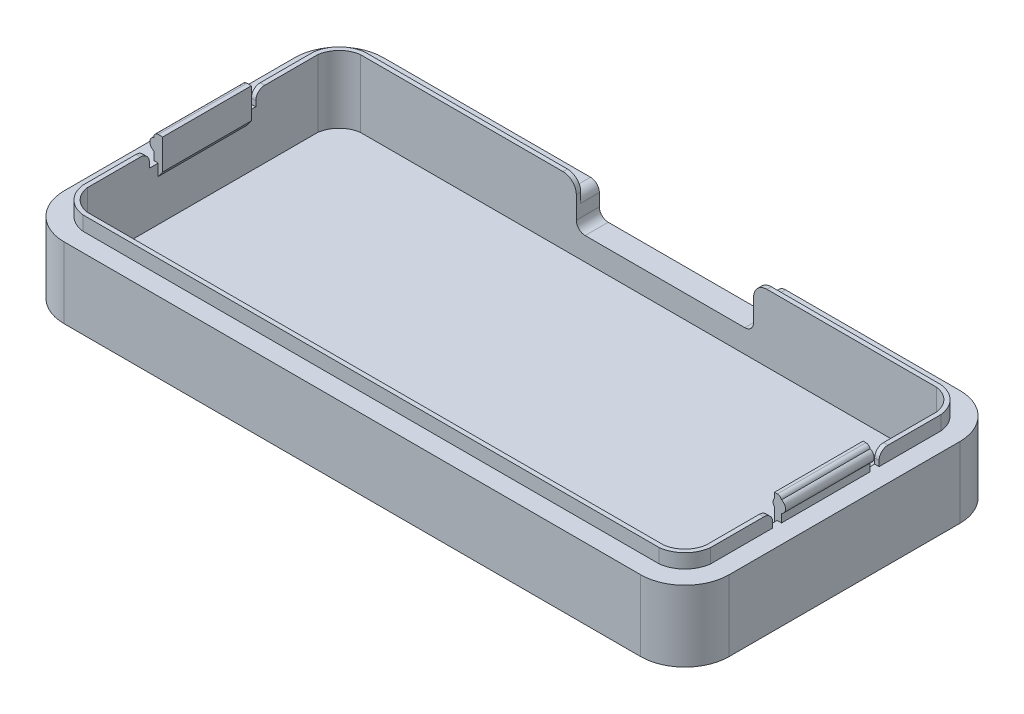
SolidWorks part; units mm, degrees
ref_plane "前视基准面" through (0, 0, 0) normal (0, 0, 1) x (1, 0, 0)
ref_plane "上视基准面" through (0, 0, 0) normal (0, 1, 0) x (1, 0, 0)
ref_plane "右视基准面" through (0, 0, 0) normal (1, 0, 0) x (0, 0, -1)
sketch "zero" plane through (0, 0, 0) normal (0, 1, 0) x (1, 0, 0)
  line L1 (-29.5, 15) -> (29.5, 15)
  line L2 (-32.5, 12) -> (-32.5, -12)
  line L3 (-29.5, -15) -> (29.5, -15)
  line L4 (32.5, 12) -> (32.5, -12)
  line L5 (-32.5, 15) -> (32.5, -15) construction
  line L6 (-32.5, -15) -> (32.5, 15) construction
  line L7 (-25.7, -15) -> (-14.5, -15)
  line L8 (-25.7, -15) -> (-25.7, -9.6569)
  line L9 (-25.7, -9.6569) -> (-14.5, -9.6569)
  line L10 (-14.5, -15) -> (-14.5, -9.6569)
  line L11 (5.2, -15) -> (12.7, -15)
  line L12 (5.2, -15) -> (5.2, -11)
  line L13 (5.2, -11) -> (12.7, -11)
  line L14 (12.7, -15) -> (12.7, -11)
  line L15 (17.8, -15) -> (25.3, -15)
  line L16 (17.8, -15) -> (17.8, -11)
  line L17 (17.8, -11) -> (25.3, -11)
  line L18 (25.3, -15) -> (25.3, -11)
  line L19 (-32.5, 7.7) -> (-19.5, 7.7)
  line L20 (-32.5, 7.7) -> (-32.5, -4.3)
  line L21 (-32.5, -4.3) -> (-19.5, -4.3)
  line L22 (-19.5, 7.7) -> (-19.5, -4.3)
  line L23 (-25.5, 14) -> (25.5, 14)
  line L24 (-25.5, 14) -> (-25.5, 8.8)
  line L25 (-25.5, 8.8) -> (25.5, 8.8)
  line L26 (25.5, 14) -> (25.5, 8.8)
  line L27 (-19.5, 7.2329) -> (-35.5, 7.2329)
  line L28 (-19.5, 7.2329) -> (-19.5, -3.7671)
  line L29 (-19.5, -3.7671) -> (-35.5, -3.7671)
  line L30 (-35.5, 7.2329) -> (-35.5, -3.7671)
  arc A0 (29.5, -15) -> (32.5, -12) centre (29.5, -12) ccw
  arc A1 (29.5, 15) -> (32.5, 12) centre (29.5, 12) cw
  arc A2 (-32.5, -12) -> (-29.5, -15) centre (-29.5, -12) ccw
  arc A3 (-29.5, 15) -> (-32.5, 12) centre (-29.5, 12) ccw
  circle A4 centre (-29, 11.4) radius 3
  circle A5 centre (-29, -11.5) radius 3
  circle A6 centre (29, 11.4) radius 3
  circle A7 centre (29, -11.5) radius 3
  circle A8 centre (-29, 11.4) radius 1.375
  circle A9 centre (-29, -11.5) radius 1.375
  circle A10 centre (29, -11.5) radius 1.375
  circle A11 centre (29, 11.4) radius 1.375
  point P0 (0, 0)
  dimension "D3" = 3
  dimension "D4" = 6
  dimension "D9" = 2.75
  dimension "D1" = 65
  dimension "D2" = 30
  dimension "D5" = 3.6
  dimension "D6" = 3.5
  dimension "D7" = 3.5
  dimension "D8" = 3.5
  dimension "D10" = 12
  dimension "D11" = 7.3
  dimension "D12" = 13
  dimension "D13" = 11.2
  dimension "D14" = 6.8
  dimension "D15" = 19.7
  dimension "D16" = 7.5
  dimension "D17" = 7.5
  dimension "D18" = 5.1
  dimension "D19" = 4
  dimension "D20" = 5.2
  dimension "D21" = 7
  dimension "D22" = 7
  dimension "D23" = 1
  dimension "D24" = 11
  dimension "D25" = 16
sketch "sugar" plane through (0, 0, 0) normal (0, 1, 0) x (1, 0, 0)
  line L1 (-29.5, 15) -> (29.5, 15)
  line L2 (-32.5, 12) -> (-32.5, -12)
  line L3 (-29.5, -15) -> (29.5, -15)
  line L4 (32.5, 12) -> (32.5, -12)
  line L5 (-32.5, 15) -> (32.5, -15) construction
  line L6 (-32.5, -15) -> (32.5, 15) construction
  line L7 (23.5, -11.5) -> (19.5, -11.5)
  line L8 (23.5, -11.5) -> (23.5, -13.9082)
  line L9 (23.5, -13.9082) -> (19.5, -13.9082)
  line L10 (19.5, -11.5) -> (19.5, -13.9082)
  line L11 (16, -11.0071) -> (8.5, -11.0071)
  line L12 (16, -11.0071) -> (16, -15)
  line L13 (16, -15) -> (8.5, -15)
  line L14 (8.5, -11.0071) -> (8.5, -15)
  line L15 (20.5, -13.9082) -> (22.5, -13.9082)
  line L16 (20.5, -13.9082) -> (20.5, -14.8173)
  line L17 (20.5, -14.8173) -> (22.5, -14.8173)
  line L18 (22.5, -13.9082) -> (22.5, -14.8173)
  arc A0 (29.5, 15) -> (32.5, 12) centre (29.5, 12) cw
  arc A1 (29.5, -15) -> (32.5, -12) centre (29.5, -12) ccw
  arc A2 (-32.5, -12) -> (-29.5, -15) centre (-29.5, -12) ccw
  arc A3 (-29.5, 15) -> (-32.5, 12) centre (-29.5, 12) ccw
  circle A4 centre (-29, 11.4) radius 3
  circle A5 centre (-29, 11.4) radius 1.375
  circle A6 centre (-29, -11.5) radius 3
  circle A7 centre (-29, -11.5) radius 1.375
  circle A8 centre (29, 11.4) radius 3
  circle A9 centre (29, 11.4) radius 1.375
  circle A10 centre (29, -11.5) radius 3
  circle A11 centre (29, -11.5) radius 1.375
  dimension "D3" = 3
  dimension "D1" = 65
  dimension "D2" = 30
  dimension "D4" = 9
  dimension "D5" = 4
  dimension "D6" = 3.5
  dimension "D7" = 7.5
  dimension "D8" = 2
  dimension "D9" = 1
sketch "case" plane through (0, 0, 0) normal (0, 1, 0) x (1, 0, 0)
  line L1 (-34.0422, 18) -> (30.9578, 18)
  line L2 (-39.0422, 13) -> (-39.0422, -13)
  line L3 (-34.0422, -18) -> (30.9578, -18)
  line L4 (35.9578, 13) -> (35.9578, -13)
  line L5 (-39.0422, 18) -> (35.9578, -18) construction
  line L6 (-39.0422, -18) -> (35.9578, 18) construction
  arc A0 (-39.0422, -13) -> (-34.0422, -18) centre (-34.0422, -13) ccw
  arc A1 (30.9578, -18) -> (35.9578, -13) centre (30.9578, -13) ccw
  arc A2 (30.9578, 18) -> (35.9578, 13) centre (30.9578, 13) cw
  arc A3 (-34.0422, 18) -> (-39.0422, 13) centre (-34.0422, 13) ccw
  point P0 (-1.5422, 0)
  point P3 (-1.5422, 0)
  dimension "D3" = 5
  dimension "D1" = 75
  dimension "D2" = 36
extrude "凸台-拉伸2" add sketch "case" along normal blind 8
sketch "草图2" plane through (0, 0, 0) normal (0, 1, 0) x (1, 0, 0)
  line L4 (-34.0422, -15.4) -> (30.9578, -15.4)
  line L5 (33.3578, -13) -> (33.3578, 13)
  line L6 (30.9578, 15.4) -> (-34.0422, 15.4)
  line L7 (-36.4422, 13) -> (-36.4422, -13)
  line L12 (33.8578, -13) -> (33.8578, 13)
  line L13 (30.9578, 15.9) -> (-34.0422, 15.9)
  line L14 (-36.9422, 13) -> (-36.9422, -13)
  line L15 (-34.0422, -15.9) -> (30.9578, -15.9)
  arc A4 (30.9578, -15.4) -> (33.3578, -13) centre (30.583, -12.6252) ccw
  arc A5 (33.3578, 13) -> (30.9578, 15.4) centre (30.583, 12.6252) ccw
  arc A6 (-34.0422, 15.4) -> (-36.4422, 13) centre (-33.6674, 12.6252) ccw
  arc A7 (-36.4422, -13) -> (-34.0422, -15.4) centre (-33.6674, -12.6252) ccw
  arc A12 (30.9578, -15.9) -> (33.8578, -13) centre (30.5796, -12.6217) ccw
  arc A13 (33.8578, 13) -> (30.9578, 15.9) centre (30.5796, 12.6217) ccw
  arc A14 (-34.0422, 15.9) -> (-36.9422, 13) centre (-33.6639, 12.6217) ccw
  arc A15 (-36.9422, -13) -> (-34.0422, -15.9) centre (-33.6639, -12.6217) ccw
ref_plane "基准面1" through (0, 8, 0) normal (0, 1, 0) x (1, 0, 0)
sketch "草图3" plane through (0, 8, 0) normal (0, 1, 0) x (1, 0, 0)
  line L4 (-34.0422, -15.4) -> (30.9578, -15.4)
  line L5 (33.3578, -13) -> (33.3578, 13)
  line L6 (30.9578, 15.4) -> (-34.0422, 15.4)
  line L7 (-36.4422, 13) -> (-36.4422, -13)
  line L8 (-34.0422, -15.4) -> (30.9578, -15.4)
  line L9 (33.3578, -13) -> (33.3578, 13)
  line L10 (30.9578, 15.4) -> (-34.0422, 15.4)
  line L11 (-36.4422, 13) -> (-36.4422, -13)
  line L12 (-36.9422, 13) -> (-36.9422, -13)
  line L13 (-34.0422, -15.9) -> (30.9578, -15.9)
  line L14 (33.8578, -13) -> (33.8578, 13)
  line L15 (30.9578, 15.9) -> (-34.0422, 15.9)
  line L16 (-36.9422, 13) -> (-36.9422, -13)
  line L17 (-34.0422, -15.9) -> (30.9578, -15.9)
  line L18 (33.8578, -13) -> (33.8578, 13)
  line L19 (30.9578, 15.9) -> (-34.0422, 15.9)
  arc A4 (30.9578, -15.4) -> (33.3578, -13) centre (30.583, -12.6252) ccw
  arc A5 (33.3578, 13) -> (30.9578, 15.4) centre (30.583, 12.6252) ccw
  arc A6 (-34.0422, 15.4) -> (-36.4422, 13) centre (-33.6674, 12.6252) ccw
  arc A7 (-36.4422, -13) -> (-34.0422, -15.4) centre (-33.6674, -12.6252) ccw
  arc A8 (30.9578, -15.4) -> (33.3578, -13) centre (30.583, -12.6252) ccw
  arc A9 (33.3578, 13) -> (30.9578, 15.4) centre (30.583, 12.6252) ccw
  arc A10 (-34.0422, 15.4) -> (-36.4422, 13) centre (-33.6674, 12.6252) ccw
  arc A11 (-36.4422, -13) -> (-34.0422, -15.4) centre (-33.6674, -12.6252) ccw
  arc A12 (-36.9422, -13) -> (-34.0422, -15.9) centre (-33.6639, -12.6217) ccw
  arc A13 (30.9578, -15.9) -> (33.8578, -13) centre (30.5796, -12.6217) ccw
  arc A14 (33.8578, 13) -> (30.9578, 15.9) centre (30.5796, 12.6217) ccw
  arc A15 (-34.0422, 15.9) -> (-36.9422, 13) centre (-33.6639, 12.6217) ccw
  arc A16 (-36.9422, -13) -> (-34.0422, -15.9) centre (-33.6639, -12.6217) ccw
  arc A17 (30.9578, -15.9) -> (33.8578, -13) centre (30.5796, -12.6217) ccw
  arc A18 (33.8578, 13) -> (30.9578, 15.9) centre (30.5796, 12.6217) ccw
  arc A19 (-34.0422, 15.9) -> (-36.9422, 13) centre (-33.6639, 12.6217) ccw
  dimension "D1" = 0
  dimension "D2" = 0
extrude "凸台-拉伸4" add sketch "草图3" along normal blind 1.6
sketch "草图5" plane through (0, 8, 0) normal (0, 1, 0) x (1, 0, 0)
  line L0 (33.3578, -13) -> (33.3578, 13) construction
  line L1 (33.0578, 5) -> (33.3578, 5)
  line L2 (33.0578, 5) -> (33.0578, -5)
  line L3 (33.0578, -5) -> (33.3578, -5)
  line L4 (33.3578, 5) -> (33.3578, -5)
  line L5 (33.0578, 5) -> (33.3578, -5) construction
  line L6 (33.0578, -5) -> (33.3578, 5) construction
  point P0 (33.2078, 0)
  dimension "D2" = 10
  dimension "D3" = 0.3
  dimension "D4" = 0
ref_plane "基准面3" through (33.8578, 0, 0) normal (1, 0, 0) x (0, 0, -1)
sketch "草图7" plane through (0, 8, 0) normal (0, 1, 0) x (1, 0, 0)
  line L0 (-36.9422, 13) -> (-36.9422, -13) construction
  line L1 (-36.9422, 5) -> (-36.4422, 5)
  line L2 (-36.9422, 5) -> (-36.9422, -5)
  line L3 (-36.9422, -5) -> (-36.4422, -5)
  line L4 (-36.4422, 5) -> (-36.4422, -5)
  line L5 (-36.4422, 13) -> (-36.4422, -13) construction
  point P10 (-36.4422, 0)
  dimension "D1" = 5
  dimension "D2" = 10
extrude "凸台-拉伸8" add sketch "草图7" along normal blind 2.8
ref_plane "基准面5" through (0, 0, 5) normal (0, 0, 1) x (1, 0, 0)
sketch "草图8" plane through (0, 0, 5) normal (0, 0, 1) x (1, 0, 0)
  line L0 (-34.0422, 8) -> (-39.0422, 8) construction
  line L1 (-36.9422, 10.8) -> (-36.9422, 9.6) construction
  circle A0 centre (-36.6922, 9.6) radius 0.7
  dimension "D1" = 1.4
  dimension "D2" = 1.6
  dimension "D3" = 0.25
extrude "凸台-拉伸9" add sketch "草图8" against normal blind 10
fillet "圆角1" radius 0.5 1 edges at (-36.9422, 10.8, 0)
ref_plane "基准面7" through (-36.9422, 0, 0) normal (-1, 0, 0) x (0, 0, 1)
sketch "草图11" plane through (-36.9422, 0, 0) normal (-1, 0, 0) x (0, 0, 1)
  line L0 (-13, 8) -> (13, 8) construction
  line L1 (5, 9.6) -> (6, 9.6)
  line L2 (5, 9.6) -> (5, 8)
  line L3 (5, 8) -> (6, 8)
  line L4 (6, 9.6) -> (6, 8)
  line L6 (-5, 9.6) -> (-6, 9.6)
  line L7 (-5, 9.6) -> (-5, 8)
  line L8 (-5, 8) -> (-6, 8)
  line L9 (-6, 9.6) -> (-6, 8)
  dimension "D1" = 1
  dimension "D2" = 1
extrude "切除-拉伸1" cut sketch "草图11" against normal blind 1.2
fillet "圆角2" radius 1 2 edges at (-36.6922, 9.6, 6) (-36.6922, 9.6, -6)
ref_plane "基准面8" through (0, 0, 0) normal (0, -1, 0) x (-1, 0, 0)
sketch "草图13" plane through (0, 8, 0) normal (0, 1, 0) x (1, 0, 0)
  line L1 (-36.4422, -5) -> (-35.9422, -5)
  line L2 (-36.4422, -5) -> (-36.4422, 5)
  line L3 (-36.4422, 5) -> (-35.9422, 5)
  line L4 (-35.9422, -5) -> (-35.9422, 5)
  dimension "D1" = 0.5
extrude "凸台-拉伸10" add sketch "草图13" along normal blind 2.8
sketch "草图14" plane through (0, 8, 0) normal (0, 1, 0) x (1, 0, 0)
  line L4 (-34.0422, -15.4) -> (30.9578, -15.4)
  line L5 (33.3578, -13) -> (33.3578, 13)
  line L6 (30.9578, 15.4) -> (-34.0422, 15.4)
  line L7 (-36.4422, 13) -> (-36.4422, -13)
  line L8 (-34.0422, -15.4) -> (30.9578, -15.4)
  line L9 (33.3578, -13) -> (33.3578, 13)
  line L10 (30.9578, 15.4) -> (-34.0422, 15.4)
  line L11 (-36.4422, 13) -> (-36.4422, -13)
  arc A4 (30.9578, -15.4) -> (33.3578, -13) centre (30.583, -12.6252) ccw
  arc A5 (33.3578, 13) -> (30.9578, 15.4) centre (30.583, 12.6252) ccw
  arc A6 (-34.0422, 15.4) -> (-36.4422, 13) centre (-33.6674, 12.6252) ccw
  arc A7 (-36.4422, -13) -> (-34.0422, -15.4) centre (-33.6674, -12.6252) ccw
  arc A8 (30.9578, -15.4) -> (33.3578, -13) centre (30.583, -12.6252) ccw
  arc A9 (33.3578, 13) -> (30.9578, 15.4) centre (30.583, 12.6252) ccw
  arc A10 (-34.0422, 15.4) -> (-36.4422, 13) centre (-33.6674, 12.6252) ccw
  arc A11 (-36.4422, -13) -> (-34.0422, -15.4) centre (-33.6674, -12.6252) ccw
  dimension "D1" = 0
extrude "切除-拉伸2" cut sketch "草图14" against normal blind 6
extrude "凸台-拉伸11" add sketch "草图13<2>" against normal blind 2
sketch "草图13<2>" plane through (0, 8, 0) normal (0, 1, 0) x (1, 0, 0) same geometry as "草图13"
extrude "凸台-拉伸12" add sketch "草图5" against normal blind 2 and the other way blind 1.6
sketch "草图17" plane through (0, 9.6, 0) normal (0, 1, 0) x (1, 0, 0)
  line L0 (33.3578, -13) -> (33.3578, -5) construction
  line L1 (33.3578, -5) -> (33.8578, -5)
  line L2 (33.3578, -5) -> (33.3578, -6)
  line L3 (33.3578, -6) -> (33.8578, -6)
  line L4 (33.8578, -5) -> (33.8578, -6)
  line L5 (33.3578, -13) -> (33.3578, 13) construction
  line L6 (33.8578, -13) -> (33.8578, 13) construction
  line L8 (33.3578, 5) -> (33.8578, 5)
  line L9 (33.3578, 5) -> (33.3578, 6)
  line L10 (33.3578, 6) -> (33.8578, 6)
  line L11 (33.8578, 5) -> (33.8578, 6)
  dimension "D1" = 1
  dimension "D2" = 1
extrude "切除-拉伸3" cut sketch "草图17" against normal blind 1.6
sketch "草图19" plane through (0, 9.6, 0) normal (0, 1, 0) x (1, 0, 0)
  line L0 (33.0578, 5) -> (33.0578, -5) construction
  line L1 (33.8578, -5) -> (33.0578, -5)
  line L2 (33.8578, -5) -> (33.8578, 5)
  line L3 (33.8578, 5) -> (33.0578, 5)
  line L4 (33.0578, -5) -> (33.0578, 5)
extrude "凸台-拉伸15" add sketch "草图19" along normal blind 1
sketch "草图20" plane through (0, 0, -5) normal (0, 0, -1) x (-1, 0, 0)
  line L0 (-30.9578, 8) -> (-35.9578, 8) construction
  line L3 (-33.8578, 8) -> (-33.8578, 10.6) construction
  circle A0 centre (-33.6078, 9.6) radius 0.7
  dimension "D1" = 1.4
  dimension "D2" = 1.6
  dimension "D3" = 0.25
extrude "凸台-拉伸16" add sketch "草图20" against normal blind 10
fillet "圆角4" radius 0.5 1 edges at (33.8578, 10.6, 0)
chamfer "倒角11" distance 1 angle 54 1 edges at (-35.9422, 6, 0) first distance on face at (-36.1922, 6, 0)
fillet "圆角5" radius 1 2 edges at (33.6078, 9.6, -6) (33.6078, 9.6, 6)
sketch "草图40" plane through (0, 0, 0) normal (0, -1, 0) x (1, 0, 0)
  line B0 (-26.7964, 4.2639) -> (-26.7964, -2.5517)
  line B1 (-11.5582, -2.5517) -> (-11.5582, 4.2639)
  line B2 (-24.8417, 5.0731) -> (-19.5762, 8.1162)
  line B3 (-18.7726, 8.1162) -> (-13.5356, 5.0674)
  line B4 (-13.5299, 4.3665) -> (-18.6188, 1.3234)
  line B5 (-17.0402, -3.8339) -> (-17.6329, -4.1644)
  line B6 (-17.6899, -4.2613) -> (-17.6899, -5.9709)
  line B7 (-17.7468, -6.0677) -> (-18.8524, -6.6946)
  line B8 (-19.0177, -6.5977) -> (-19.0177, -1.3208)
  line B9 (-18.9607, -1.2239) -> (-17.0801, -0.1582)
  line B10 (-13.1367, -3.4806) -> (-14.2308, -4.1017)
  line B11 (-14.3961, -4.0048) -> (-14.3961, -1.4917)
  line B12 (-14.3391, -1.3948) -> (-13.245, -0.7794)
  line B13 (-13.0797, -0.8763) -> (-13.0797, -3.3837)
  line B14 (-17.1087, -2.8195) -> (-17.6329, -3.0817)
  line B15 (-17.6899, -2.962) -> (-17.6899, -1.6171)
  line B16 (-17.6329, -1.5202) -> (-17.1428, -1.2467)
  line B17 (-17.6329, -3.0817) -> (-17.6329, -4.1644)
  line B18 (-17.6899, -2.962) -> (-17.6899, -4.2613)
  spline B19 degree 3 poles (-18.3167, 9.1591) (-18.5846, 9.3072) (-18.8809, 9.387) (-19.1772, 9.387) knots 3 3 3 3 4 4 4 4
  spline B20 degree 3 poles (-19.1772, 9.387) (-19.4736, 9.387) (-19.7699, 9.3072) (-20.0377, 9.1591) knots 4 4 4 4 5 5 5 5
  spline B21 degree 3 poles (-25.9359, 5.7513) (-26.4658, 5.4435) (-26.7964, 4.8737) (-26.7964, 4.2639) knots 8 8 8 8 9 9 9 9
  spline B22 degree 3 poles (-26.7964, -2.5517) (-26.7964, -3.1671) (-26.4658, -3.7313) (-25.9359, -4.039) knots 10 10 10 10 11 11 11 11
  spline B23 degree 3 poles (-20.0377, -7.4468) (-19.7699, -7.6007) (-19.4736, -7.6748) (-19.1772, -7.6748) knots 14 14 14 14 15 15 15 15
  spline B24 degree 3 poles (-19.1772, -7.6748) (-18.8809, -7.6748) (-18.5846, -7.6007) (-18.3167, -7.4468) knots 15 15 15 15 16 16 16 16
  spline B25 degree 3 poles (-12.4187, -4.039) (-11.883, -3.7313) (-11.5582, -3.1671) (-11.5582, -2.5517) knots 19 19 19 19 20 20 20 20
  spline B26 degree 3 poles (-11.5582, 4.2639) (-11.5582, 4.8737) (-11.883, 5.4435) (-12.4187, 5.7513) knots 21 21 21 21 22 22 22 22
  spline B27 degree 2 poles (-19.73, 1.3234) (-24.8816, 4.2981) (-24.893, 4.3038) knots 0 0 0 1 1 1
  spline B28 degree 3 poles (-24.893, 4.3038) (-25.1608, 4.4975) (-25.1323, 4.9079) (-24.8417, 5.0731) knots 1 1 1 1 2 2 2 2
  spline B29 degree 3 poles (-19.5762, 8.1162) (-19.3311, 8.2587) (-19.0233, 8.2587) (-18.7726, 8.1162) knots 3 3 3 3 4 4 4 4
  spline B30 degree 3 poles (-13.5356, 5.0674) (-13.2678, 4.9136) (-13.2621, 4.5261) (-13.5299, 4.3665) knots 5 5 5 5 6 6 6 6
  spline B31 degree 3 poles (-18.6188, 1.3234) (-18.9607, 1.124) (-19.3881, 1.124) (-19.73, 1.3234) knots 7 7 7 7 8 8 8 8
  spline B32 degree 3 poles (-17.6899, -5.9709) (-17.6899, -6.0108) (-17.707, -6.045) (-17.7468, -6.0677) knots 3 3 3 3 4 4 4 4
  spline B33 degree 3 poles (-18.8524, -6.6946) (-18.9265, -6.7345) (-19.0177, -6.6832) (-19.0177, -6.5977) knots 5 5 5 5 6 6 6 6
  spline B34 degree 3 poles (-19.0177, -1.3208) (-19.0177, -1.2809) (-19.0006, -1.241) (-18.9607, -1.2239) knots 7 7 7 7 8 8 8 8
  spline B35 degree 3 poles (-17.0801, -0.1582) (-15.8606, 0.5313) (-14.852, 0.6681) (-14.852, -0.6996) knots 9 9 9 9 10 10 10 10
  spline B36 degree 3 poles (-14.852, -0.6996) (-14.852, -2.016) (-15.872, -3.1728) (-17.0402, -3.8339) knots 10 10 10 10 11 11 11 11
  spline B37 degree 3 poles (-13.0797, -3.3837) (-13.0797, -3.4236) (-13.1025, -3.4635) (-13.1367, -3.4806) knots 0 0 0 0 1 1 1 1
  spline B38 degree 3 poles (-14.2308, -4.1017) (-14.3049, -4.1416) (-14.3961, -4.0903) (-14.3961, -4.0048) knots 2 2 2 2 3 3 3 3
  spline B39 degree 3 poles (-14.3961, -1.4917) (-14.3961, -1.4518) (-14.3733, -1.4176) (-14.3391, -1.3948) knots 4 4 4 4 5 5 5 5
  spline B40 degree 3 poles (-13.245, -0.7794) (-13.1709, -0.7395) (-13.0797, -0.7908) (-13.0797, -0.8763) knots 6 6 6 6 7 7 7 7
  spline B41 degree 3 poles (-16.1513, -1.4347) (-16.1513, -1.9761) (-16.4589, -2.4548) (-17.1087, -2.8195) knots 0 0 0 0 1 1 1 1
  spline B42 degree 3 poles (-17.6899, -1.6171) (-17.6899, -1.5772) (-17.6671, -1.5373) (-17.6329, -1.5202) knots 4 4 4 4 5 5 5 5
  spline B43 degree 3 poles (-17.1428, -1.2467) (-16.5046, -0.882) (-16.1513, -0.8763) (-16.1513, -1.4347) knots 6 6 6 6 7 7 7 7
  line B44 (-12.4187, 5.7513) -> (-13.2393, 6.2243)
  line B45 (-13.2393, 6.2243) -> (-17.4961, 8.6804)
  line B46 (-17.4961, 8.6804) -> (-18.3167, 9.1591)
  line B47 (-20.0377, 9.1591) -> (-20.8584, 8.6804)
  line B48 (-20.8584, 8.6804) -> (-25.1152, 6.2243)
  line B49 (-25.1152, 6.2243) -> (-25.9359, 5.7513)
  line B50 (-25.9359, -4.039) -> (-25.1152, -4.512)
  line B51 (-25.1152, -4.512) -> (-20.8584, -6.9681)
  line B52 (-20.8584, -6.9681) -> (-20.0377, -7.4468)
  line B53 (-18.3167, -7.4468) -> (-17.4961, -6.9681)
  line B54 (-17.4961, -6.9681) -> (-13.2393, -4.512)
  line B55 (-13.2393, -4.512) -> (-12.4187, -4.039)
  line B56 (-7.5634, 3.7852) -> (-9.4383, 3.7852)
  line B57 (-9.4383, 3.7852) -> (-9.4383, -2.7796)
  line B58 (-9.4383, -2.7796) -> (-8.6062, -2.7796)
  line B59 (-8.6062, -2.7796) -> (-8.6062, -0.1753)
  line B60 (-8.6062, -0.1753) -> (-7.5178, -0.1753)
  line B61 (-7.626, 0.4971) -> (-8.6062, 0.4971)
  line B62 (-8.6062, 0.4971) -> (-8.6062, 3.1128)
  line B63 (-8.6062, 3.1128) -> (-7.6602, 3.1128)
  line B64 (-4.0246, 2.087) -> (-4.0246, -2.7796)
  line B65 (-4.0246, -2.7796) -> (-3.2096, -2.7796)
  line B66 (-3.2096, -2.7796) -> (-3.2096, 2.087)
  line B67 (-3.2096, 2.087) -> (-4.0246, 2.087)
  line B68 (1.4975, 1.01) -> (0.6655, 1.3405)
  line B69 (1.8223, 2.1269) -> (2.6201, 3.1299)
  line B70 (-0.611, 0.1666) -> (0.2381, -0.1924)
  line B71 (-1.312, -0.8421) -> (-2.218, -1.9476)
  line B72 (6.6035, 2.315) -> (6.6035, -1.0244)
  line B73 (5.1617, -0.6369) -> (5.1617, 2.315)
  line B74 (5.1617, 2.315) -> (3.5718, 2.315)
  line B75 (3.5718, 2.315) -> (3.5718, -0.8364)
  line B76 (6.7517, -2.0787) -> (6.7858, -2.0787)
  line B77 (6.7858, -2.0787) -> (6.8998, -2.7796)
  line B78 (6.8998, -2.7796) -> (8.1991, -2.7796)
  line B79 (8.1991, -2.7796) -> (8.1991, 2.315)
  line B80 (8.1991, 2.315) -> (6.6035, 2.315)
  line B81 (12.0514, -1.7766) -> (11.2479, -1.7766)
  line B82 (13.1455, 1.1638) -> (13.9319, 1.1638)
  line B83 (13.9319, 1.1638) -> (13.9319, 2.315)
  line B84 (13.9319, 2.315) -> (12.0628, 2.315)
  line B85 (9.8118, -0.7281) -> (9.8118, -0.7623)
  line B86 (9.7149, -2.5916) -> (9.7149, -2.6371)
  line B87 (11.265, -2.9962) -> (11.7494, -2.9962)
  line B88 (14.3878, 1.7736) -> (14.9463, 0.725)
  line B89 (17.1916, -2.2668) -> (17.2314, -2.2668)
  line B90 (17.2314, -2.2668) -> (17.3454, -2.7796)
  line B91 (17.3454, -2.7796) -> (18.6447, -2.7796)
  line B92 (18.6447, -2.7796) -> (18.6447, 0.1153)
  line B93 (17.0491, -0.4489) -> (17.0491, -1.2638)
  line B94 (21.1351, 1.4317) -> (21.1008, 1.4317)
  line B95 (21.1008, 1.4317) -> (20.9926, 2.315)
  line B96 (20.9926, 2.315) -> (19.6933, 2.315)
  line B97 (19.6933, 2.315) -> (19.6933, -2.7796)
  line B98 (19.6933, -2.7796) -> (21.2775, -2.7796)
  line B99 (21.2775, -2.7796) -> (21.2775, 0.1324)
  line B100 (22.9358, 0.9644) -> (23.2036, 2.3378)
  spline B101 degree 3 poles (-13.735, 0.8903) (-13.2962, 1.1411) (-12.9828, 1.0328) (-12.9828, 0.6339) (-12.9828, 0.2407) (-13.2962, -0.2209) (-13.735, -0.466) knots 2 2 2 2 3 3 3 4 4 4 4
  spline B102 degree 3 poles (-13.735, -0.466) (-14.1795, -0.7224) (-14.4929, -0.6141) (-14.4929, -0.2209) (-14.4929, 0.1837) (-14.1795, 0.6396) (-13.735, 0.8903) knots 0 0 0 0 1 1 1 2 2 2 2
  spline B103 degree 3 poles (-7.5178, -0.1753) (-6.0874, -0.1753) (-5.1016, 0.4743) (-5.1016, 1.8591) knots 5 5 5 5 6 6 6 6
  spline B104 degree 3 poles (-5.1016, 1.8591) (-5.1016, 3.2951) (-6.0874, 3.7852) (-7.5634, 3.7852) knots 6 6 6 6 7 7 7 7
  spline B105 degree 3 poles (-7.6602, 3.1128) (-6.5091, 3.1128) (-5.9278, 2.8108) (-5.9278, 1.8591) knots 3 3 3 3 4 4 4 4
  spline B106 degree 3 poles (-5.9278, 1.8591) (-5.9278, 0.9188) (-6.4692, 0.4971) (-7.626, 0.4971) knots 4 4 4 4 5 5 5 5
  spline B107 degree 3 poles (-3.6142, 3.09) (-3.2894, 3.09) (-3.0501, 3.3123) (-3.0501, 3.6143) (-3.0501, 3.9505) (-3.2894, 4.1442) (-3.6142, 4.1442) knots 2 2 2 2 3 3 3 4 4 4 4
  spline B108 degree 3 poles (-3.6142, 4.1442) (-3.939, 4.1442) (-4.1784, 3.9505) (-4.1784, 3.6143) (-4.1784, 3.3123) (-3.939, 3.09) (-3.6142, 3.09) knots 0 0 0 0 1 1 1 2 2 2 2
  spline B109 degree 3 poles (0.6655, 1.3405) (0.0785, 1.5742) (-0.3432, 1.7166) (-0.3432, 2.087) knots 1 1 1 1 2 2 2 2
  spline B110 degree 3 poles (-0.3432, 2.087) (-0.3432, 2.4403) (-0.0411, 2.6398) (0.4546, 2.6398) knots 2 2 2 2 3 3 3 3
  spline B111 degree 3 poles (0.4546, 2.6398) (0.9732, 2.6398) (1.3835, 2.4632) (1.8223, 2.1269) knots 3 3 3 3 4 4 4 4
  spline B112 degree 3 poles (2.6201, 3.1299) (2.0389, 3.7168) (1.2239, 4.0132) (0.4546, 4.0132) knots 5 5 5 5 6 6 6 6
  spline B113 degree 3 poles (0.4546, 4.0132) (-0.9643, 4.0132) (-1.9673, 3.1128) (-1.9673, 1.9959) knots 6 6 6 6 7 7 7 7
  spline B114 degree 3 poles (-1.9673, 1.9959) (-1.9673, 1.0271) (-1.312, 0.4458) (-0.611, 0.1666) knots 7 7 7 7 8 8 8 8
  spline B115 degree 3 poles (0.2381, -0.1924) (0.8079, -0.4318) (1.1784, -0.5572) (1.1784, -0.9447) knots 9 9 9 9 10 10 10 10
  spline B116 degree 3 poles (1.1784, -0.9447) (1.1784, -1.3037) (0.8991, -1.5259) (0.3065, -1.5259) knots 10 10 10 10 11 11 11 11
  spline B117 degree 3 poles (0.3065, -1.5259) (-0.2178, -1.5259) (-0.839, -1.2467) (-1.312, -0.8421) knots 11 11 11 11 12 12 12 12
  spline B118 degree 3 poles (-2.218, -1.9476) (-1.5285, -2.5802) (-0.594, -2.905) (0.2722, -2.905) knots 13 13 13 13 14 14 14 14
  spline B119 degree 3 poles (0.2722, -2.905) (1.885, -2.905) (2.8195, -1.9305) (2.8195, -0.8193) knots 14 14 14 14 15 15 15 15
  spline B120 degree 3 poles (2.8195, -0.8193) (2.8195, 0.121) (2.3238, 0.6795) (1.4975, 1.01) knots 15 15 15 15 16 16 16 16
  spline B121 degree 3 poles (6.6035, -1.0244) (6.3357, -1.4005) (6.1134, -1.543) (5.7544, -1.543) knots 1 1 1 1 2 2 2 2
  spline B122 degree 3 poles (5.7544, -1.543) (5.3498, -1.543) (5.1617, -1.3436) (5.1617, -0.6369) knots 2 2 2 2 3 3 3 3
  spline B123 degree 3 poles (3.5718, -0.8364) (3.5718, -2.1072) (4.0448, -2.905) (5.156, -2.905) knots 6 6 6 6 7 7 7 7
  spline B124 degree 3 poles (5.156, -2.905) (5.8512, -2.905) (6.33, -2.5802) (6.7517, -2.0787) knots 7 7 7 7 8 8 8 8
  spline B125 degree 3 poles (11.2479, -1.7766) (10.7008, -1.7766) (10.4957, -1.6684) (10.4957, -1.4347) knots 1 1 1 1 2 2 2 2
  spline B126 degree 3 poles (10.4957, -1.4347) (10.4957, -1.2638) (10.5355, -1.184) (10.6552, -1.0757) knots 2 2 2 2 3 3 3 3
  spline B127 degree 3 poles (10.6552, -1.0757) (10.8775, -1.1384) (11.0826, -1.1669) (11.2536, -1.1669) knots 3 3 3 3 4 4 4 4
  spline B128 degree 3 poles (11.2536, -1.1669) (12.3819, -1.1669) (13.288, -0.6483) (13.288, 0.5427) knots 4 4 4 4 5 5 5 5
  spline B129 degree 3 poles (13.288, 0.5427) (13.288, 0.7878) (13.2253, 1.0214) (13.1455, 1.1638) knots 5 5 5 5 6 6 6 6
  spline B130 degree 3 poles (12.0628, 2.315) (11.8291, 2.4004) (11.5499, 2.4403) (11.2536, 2.4403) knots 9 9 9 9 10 10 10 10
  spline B131 degree 3 poles (11.2536, 2.4403) (10.1538, 2.4403) (9.1223, 1.8363) (9.1223, 0.5883) knots 10 10 10 10 11 11 11 11
  spline B132 degree 3 poles (9.1223, 0.5883) (9.1223, -0.0044) (9.4528, -0.4774) (9.8118, -0.7281) knots 11 11 11 11 12 12 12 12
  spline B133 degree 3 poles (9.8118, -0.7623) (9.4813, -0.9959) (9.2476, -1.3549) (9.2476, -1.714) knots 13 13 13 13 14 14 14 14
  spline B134 degree 3 poles (9.2476, -1.714) (9.2476, -2.1414) (9.4471, -2.4092) (9.7149, -2.5916) knots 14 14 14 14 15 15 15 15
  spline B135 degree 3 poles (9.7149, -2.6371) (9.2419, -2.8765) (8.9912, -3.2184) (8.9912, -3.6401) knots 16 16 16 16 17 17 17 17
  spline B136 degree 3 poles (8.9912, -3.6401) (8.9912, -4.5519) (9.9542, -4.9223) (11.1282, -4.9223) knots 17 17 17 17 18 18 18 18
  spline B137 degree 3 poles (11.1282, -4.9223) (12.9005, -4.9223) (14.0118, -4.1587) (14.0118, -3.0817) knots 18 18 18 18 19 19 19 19
  spline B138 degree 3 poles (14.0118, -3.0817) (14.0118, -2.1585) (13.3051, -1.7766) (12.0514, -1.7766) knots 19 19 19 19 20 20 20 20
  spline B139 degree 3 poles (11.2536, -0.2095) (10.8889, -0.2095) (10.6097, 0.0583) (10.6097, 0.5883) (10.6097, 1.1069) (10.8889, 1.3747) (11.2536, 1.3747) knots 2 2 2 2 3 3 3 4 4 4 4
  spline B140 degree 3 poles (11.2536, 1.3747) (11.6297, 1.3747) (11.8975, 1.1069) (11.8975, 0.5883) (11.8975, 0.0583) (11.6297, -0.2095) (11.2536, -0.2095) knots 0 0 0 0 1 1 1 2 2 2 2
  spline B141 degree 3 poles (11.3789, -3.925) (10.7236, -3.925) (10.2962, -3.7484) (10.2962, -3.3894) knots 0 0 0 0 1 1 1 1
  spline B142 degree 3 poles (10.2962, -3.3894) (10.2962, -3.2184) (10.3759, -3.076) (10.5355, -2.9335) knots 1 1 1 1 2 2 2 2
  spline B143 degree 3 poles (10.5355, -2.9335) (10.7008, -2.9791) (10.8946, -2.9962) (11.265, -2.9962) knots 2 2 2 2 3 3 3 3
  spline B144 degree 3 poles (11.7494, -2.9962) (12.2223, -2.9962) (12.4902, -3.0588) (12.4902, -3.3609) knots 4 4 4 4 5 5 5 5
  spline B145 degree 3 poles (12.4902, -3.3609) (12.4902, -3.6857) (12.0343, -3.925) (11.3789, -3.925) knots 5 5 5 5 6 6 6 6
  spline B146 degree 3 poles (16.5819, 2.4403) (15.7897, 2.4403) (15.0603, 2.1725) (14.3878, 1.7736) knots 0 0 0 0 1 1 1 1
  spline B147 degree 3 poles (14.9463, 0.725) (15.4535, 1.01) (15.8752, 1.1696) (16.2798, 1.1696) knots 2 2 2 2 3 3 3 3
  spline B148 degree 3 poles (16.2798, 1.1696) (16.7983, 1.1696) (17.015, 0.9302) (17.0491, 0.5199) knots 3 3 3 3 4 4 4 4
  spline B149 degree 3 poles (17.0491, 0.5199) (15.0603, 0.3033) (14.2168, -0.2779) (14.2168, -1.3549) knots 4 4 4 4 5 5 5 5
  spline B150 degree 3 poles (14.2168, -1.3549) (14.2168, -2.204) (14.7924, -2.905) (15.7328, -2.905) knots 5 5 5 5 6 6 6 6
  spline B151 degree 3 poles (15.7328, -2.905) (16.2969, -2.905) (16.7699, -2.6428) (17.1916, -2.2668) knots 6 6 6 6 7 7 7 7
  spline B152 degree 3 poles (18.6447, 0.1153) (18.6447, 1.7109) (17.8982, 2.4403) (16.5819, 2.4403) knots 11 11 11 11 12 12 12 12
  spline B153 degree 3 poles (17.0491, -1.2638) (16.8154, -1.5145) (16.6046, -1.6684) (16.2798, -1.6684) knots 0 0 0 0 1 1 1 1
  spline B154 degree 3 poles (16.2798, -1.6684) (15.9492, -1.6684) (15.7328, -1.5259) (15.7328, -1.2296) knots 1 1 1 1 2 2 2 2
  spline B155 degree 3 poles (15.7328, -1.2296) (15.7328, -0.8706) (16.0576, -0.5856) (17.0491, -0.4489) knots 2 2 2 2 3 3 3 3
  spline B156 degree 3 poles (22.5882, 2.4403) (22.0753, 2.4403) (21.5111, 2.1098) (21.1351, 1.4317) knots 0 0 0 0 1 1 1 1
  spline B157 degree 3 poles (21.2775, 0.1324) (21.5454, 0.8048) (22.0013, 1.0442) (22.3773, 1.0442) knots 7 7 7 7 8 8 8 8
  spline B158 degree 3 poles (22.3773, 1.0442) (22.6053, 1.0442) (22.7535, 1.01) (22.9358, 0.9644) knots 8 8 8 8 9 9 9 9
  spline B159 degree 3 poles (23.2036, 2.3378) (23.0612, 2.4004) (22.8902, 2.4403) (22.5882, 2.4403) knots 10 10 10 10 11 11 11 11
sketch_block_instance "块1-4"
sketch_block "块1"
chamfer "倒角12" distance 1 angle 45 1 edges at (33.0578, 6, 0)
sketch "草图41" plane through (0, 9.6, 0) normal (0, 1, 0) x (1, 0, 0)
  line L0 (30.9578, 18) -> (-34.0422, 18) construction
  line L1 (10.3097, 15.3708) -> (-9.6903, 15.3708)
  line L2 (10.3097, 15.3708) -> (10.3097, 18)
  line L3 (10.3097, 18) -> (-9.6903, 18)
  line L4 (-9.6903, 15.3708) -> (-9.6903, 18)
  line L5 (35.9578, -13) -> (35.9578, 13) construction
  dimension "D1" = 20
  dimension "D2" = 25.6481
extrude "切除-拉伸15" cut sketch "草图41" against normal blind 5
fillet "圆角6" radius 1.5 2 edges at (10.3097, 9.6, -15.65) (-9.6903, 9.6, -15.65)
fillet "圆角7" radius 1 4 edges at (10.3097, 4.6, -16.7) (-9.6903, 4.6, -16.7) (10.3097, 8, -16.95) (-9.6903, 8, -16.95)
extrude "切除-拉伸16" cut sketch "草图40" against normal blind 0.5
